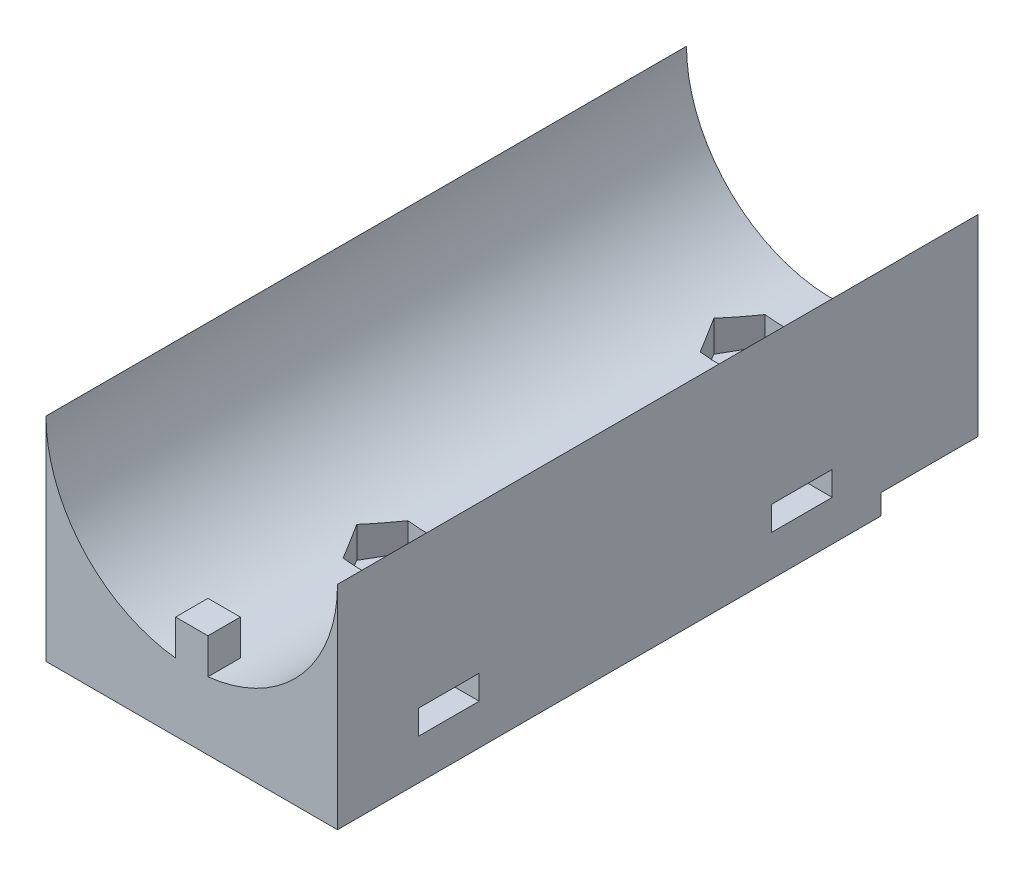
SolidWorks part; units mm, degrees
ref_plane "Plan de face" through (0, 0, 0) normal (0, 0, 1) x (1, 0, 0)
ref_plane "Plan de dessus" through (0, 0, 0) normal (0, 1, 0) x (1, 0, 0)
ref_plane "Plan de droite" through (0, 0, 0) normal (1, 0, 0) x (0, 0, -1)
sketch "Esquisse1" plane through (0, 0, 1608.5531) normal (0, 0, 1) x (1, 0, 0)
  line L0 (0, 17.4989) -> (36, 17.4989) construction
  line L1 (0, 0) -> (36, 0)
  line L2 (0, 26.25) -> (0, 0)
  line L6 (0, 26.25) -> (36, 26.25) construction
  line L8 (36, 26.25) -> (36, 0)
  arc A0 (0, 26.25) -> (36, 26.25) centre (18, 26.25) ccw
extrude "Boss.-Extru.1" add sketch "Esquisse1" along normal blind 79.1
sketch "Esquisse7" plane through (36, 0, 0) normal (1, 0, 0) x (0, 0, -1)
  line L0 (-1687.6531, 0) -> (-1608.5531, 0) construction
  line L1 (-1677.6531, 8) -> (-1670.1531, 8)
  line L2 (-1677.6531, 8) -> (-1677.6531, 5)
  line L3 (-1677.6531, 5) -> (-1670.1531, 5)
  line L4 (-1670.1531, 8) -> (-1670.1531, 5)
  line L5 (-1634.0531, 8) -> (-1626.5531, 8)
  line L6 (-1634.0531, 8) -> (-1634.0531, 5)
  line L7 (-1634.0531, 5) -> (-1626.5531, 5)
  line L8 (-1626.5531, 8) -> (-1626.5531, 5)
  line L10 (-1687.6531, 0) -> (-1687.6531, 26.25) construction
  line L11 (-1608.5531, 0) -> (-1608.5531, 26.25) construction
  dimension "D1" = 3
  dimension "D2" = 7.5
  dimension "D3" = 7.5
  dimension "D4" = 3
  dimension "D5" = 5
  dimension "D6" = 5
  dimension "D7" = 10
  dimension "D8" = 18
extrude "Boss.-Extru.3" add sketch "Esquisse7" along direction (-1, 0, 0) on the side against the normal up to surface (36 mm away) up to face at (0, 13.125, 1648.1031)
extrude "Enlèv. mat.-Extru.5" cut sketch "Esquisse7<2>" along direction (-1, 0, 0) on the side against the normal up to surface (36 mm away) up to face at (0, 13.125, 1648.1031)
sketch "Esquisse7<2>" plane through (36, 0, 0) normal (1, 0, 0) x (0, 0, -1) same geometry as "Esquisse7"
sketch "Esquisse9" plane through (0, 0, 0) normal (0, -1, 0) x (1, 0, 0)
  line L0 (20, 1683.6531) -> (20, 1687.6531)
  line L1 (20, 1683.6531) -> (16, 1683.6531)
  line L2 (20, 1687.6531) -> (16, 1687.6531)
  line L3 (16, 1683.6531) -> (16, 1687.6531)
  line L4 (20, 1683.6531) -> (16, 1687.6531) construction
  line L5 (20, 1687.6531) -> (16, 1683.6531) construction
  line L6 (0, 1687.6531) -> (0, 1608.5531) construction
  line L8 (0, 1687.6531) -> (36, 1687.6531) construction
  point P1 (18, 1685.6531)
  dimension "D1" = 4
  dimension "D2" = 4
  dimension "D3" = 16
  dimension "D4" = 0
extrude "Boss.-Extru.6" add sketch "Esquisse9" against normal blind 12.75
sketch "Esquisse11" plane through (0, 0, 0) normal (0, -1, 0) x (1, 0, 0)
  line L0 (0, 1608.5531) -> (36, 1608.5531) construction
  line L1 (0, 1687.6531) -> (36, 1687.6531) construction
  line L2 (0, 1687.6531) -> (0, 1608.5531) construction
  circle A0 centre (18, 1662.6531) radius 2.5
  circle A1 centre (18, 1618.5531) radius 2.5
  dimension "D3" = 18
  dimension "D1" = 10
  dimension "D2" = 25
  dimension "D4" = 18
extrude "Enlèv. mat.-Extru.6" cut sketch "Esquisse11" against normal blind 10
sketch "Esquisse12" plane through (0, 0, 0) normal (0, -1, 0) x (1, 0, 0)
  line L0 (0, 1687.6531) -> (36, 1687.6531) construction
  line L1 (20.3094, 1622.5531) -> (15.6906, 1622.5531)
  line L2 (15.6906, 1622.5531) -> (13.3812, 1618.5531)
  line L3 (13.3812, 1618.5531) -> (15.6906, 1614.5531)
  line L4 (15.6906, 1614.5531) -> (20.3094, 1614.5531)
  line L5 (20.3094, 1614.5531) -> (22.6188, 1618.5531)
  line L6 (22.6188, 1618.5531) -> (20.3094, 1622.5531)
  line L7 (20.3094, 1666.6531) -> (15.6906, 1666.6531)
  line L8 (15.6906, 1666.6531) -> (13.3812, 1662.6531)
  line L9 (13.3812, 1662.6531) -> (15.6906, 1658.6531)
  line L10 (15.6906, 1658.6531) -> (20.3094, 1658.6531)
  line L11 (20.3094, 1658.6531) -> (22.6188, 1662.6531)
  line L12 (22.6188, 1662.6531) -> (20.3094, 1666.6531)
  line L13 (0, 1608.5531) -> (36, 1608.5531) construction
  circle A0 centre (18, 1618.5531) radius 4 construction
  circle A1 centre (18, 1662.6531) radius 4 construction
  dimension "D1" = 8
  dimension "D2" = 8
  dimension "D3" = 0
  dimension "D4" = 0
extrude "Enlèv. mat.-Extru.12" cut sketch "Esquisse12" against normal blind 10 from offset 5 offset against normal yes
sketch "Esquisse13" plane through (0, 0, 0) normal (0, -1, 0) x (1, 0, 0)
  line L0 (0, 1608.5531) -> (36, 1608.5531) construction
  line L1 (36, 1608.5531) -> (24.5, 1608.5531)
  line L2 (36, 1608.5531) -> (36, 1620.5531)
  line L3 (36, 1620.5531) -> (24.5, 1620.5531)
  line L4 (24.5, 1608.5531) -> (24.5, 1620.5531)
  line L5 (36, 1687.6531) -> (36, 1608.5531) construction
  line L7 (0, 1608.5531) -> (11.5, 1608.5531)
  line L8 (0, 1608.5531) -> (0, 1620.5531)
  line L9 (0, 1620.5531) -> (11.5, 1620.5531)
  line L10 (11.5, 1608.5531) -> (11.5, 1620.5531)
  dimension "D1" = 11.5
  dimension "D2" = 11.5
  dimension "D3" = 12
  dimension "D4" = 12
extrude "Enlèv. mat.-Extru.13" cut sketch "Esquisse13" against normal blind 2.5
